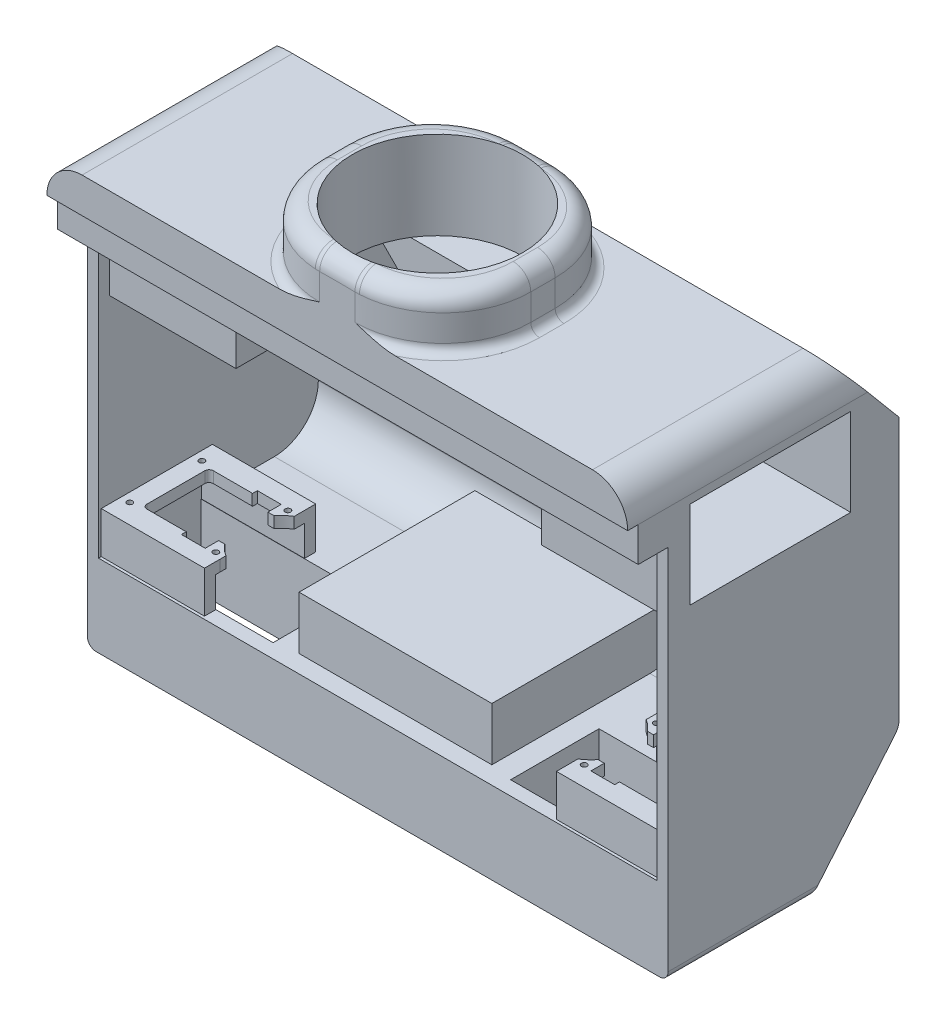
SolidWorks part; units mm, degrees
material "PLA"
ref_plane "Front Plane" through (0, 0, 0) normal (0, 0, 1) x (1, 0, 0)
ref_plane "Top Plane" through (0, 0, 0) normal (0, 1, 0) x (1, 0, 0)
ref_plane "Right Plane" through (0, 0, 0) normal (1, 0, 0) x (0, 0, -1)
sketch "Sketch1" plane through (0, 0, 0) normal (0, 1, 0) x (1, 0, 0)
  line L0 (0, -25.4) -> (0, 28.6) construction
  line L1 (-82.55, -25.4) -> (82.55, -25.4)
  line L2 (-82.55, -25.4) -> (-82.55, 28.6)
  line L3 (-82.55, 28.6) -> (82.55, 28.6)
  line L4 (82.55, -25.4) -> (82.55, 28.6)
  line L5 (-82.55, 1.6) -> (82.55, 1.6) construction
  point P4 (0, -25.4)
  point P5 (-82.55, 1.6)
  point P8 (0, 0)
  point P12 (0, 0)
  dimension "D1" = 165.1
  dimension "D2" = 54
extrude "Boss-Extrude1" add sketch "Sketch1" along normal blind 6.35
sketch "Sketch6" plane through (-82.55, 0, 0) normal (-1, 0, 0) x (0, 0, 1)
  line L1 (-37.0827, 90) -> (-37.0827, 6.35)
  line L4 (-40.2577, 90) -> (-37.0827, 90)
  line L7 (-28.6, 6.35) -> (-28.6, 0)
  line L8 (-28.6, 6.35) -> (-37.0827, 6.35)
  line L9 (-28.6, 0) -> (-40.2577, 0)
  line L10 (-40.2577, 0) -> (-40.2577, 90)
  dimension "D4" = 3.175
extrude "Boss-Extrude2" add sketch "Sketch6" against normal up to surface (165.1 mm away) up to face at (82.55, 3.175, -1.6)
sketch "Sketch7" plane through (0, 0, 25.4) normal (0, 0, 1) x (1, 0, 0)
  line L0 (-82.55, 0) -> (82.55, 0) construction
  line L1 (-82.55, 90) -> (-79.375, 90)
  line L2 (-82.55, 90) -> (-82.55, 0)
  line L3 (-82.55, 0) -> (-79.375, 0)
  line L4 (-79.375, 90) -> (-79.375, 0)
  line L6 (82.55, 0) -> (79.375, 0)
  line L7 (82.55, 0) -> (82.55, 90)
  line L8 (82.55, 90) -> (79.375, 90)
  line L9 (79.375, 0) -> (79.375, 90)
  dimension "D1" = 3.175
  dimension "D2" = 3.175
extrude "Boss-Extrude3" add sketch "Sketch7" against normal up to surface (62.4827 mm away) up to face at (0, 48.175, -37.0827)
sketch "Sketch9" plane through (0, 0, -40.2577) normal (0, 0, -1) x (-1, 0, 0)
  line L0 (-82.55, 0) -> (-82.55, 90) construction
  line L5 (82.55, 90) -> (82.55, 0) construction
  line L6 (-82.55, 0) -> (82.55, 0) construction
  line L7 (-82.55, 90) -> (82.55, 90) construction
  line L8 (-65.55, 83) -> (65.55, 83)
  line L9 (-67.55, 81) -> (-67.55, 32)
  line L10 (-65.55, 30) -> (65.55, 30)
  line L16 (67.55, 81) -> (67.55, 32)
  arc A0 (-67.55, 32) -> (-65.55, 30) centre (-65.55, 32) ccw
  arc A1 (65.55, 30) -> (67.55, 32) centre (65.55, 32) ccw
  arc A2 (65.55, 83) -> (67.55, 81) centre (65.55, 81) cw
  arc A3 (-65.55, 83) -> (-67.55, 81) centre (-65.55, 81) ccw
  dimension "D5" = 2
  dimension "D1" = 7
  dimension "D2" = 15
  dimension "D3" = 15
  dimension "D4" = 30
extrude "Boss-Extrude4" add sketch "Sketch9" along normal blind 1
sketch "Sketch10" plane through (-82.55, 0, 0) normal (-1, 0, 0) x (0, 0, 1)
  line L0 (25.4, 0) -> (25.4, 42.35) construction
  line L1 (25.4, 90) -> (25.4, 0) construction
  line L2 (25.4, 42.35) -> (-34.6, 42.35)
  line L3 (-34.6, 42.35) -> (-34.6, 90)
  line L5 (-34.6, 90) -> (25.4, 90)
  line L6 (25.4, 90) -> (25.4, 42.35)
  dimension "D1" = 42.35
  dimension "D2" = 60
extrude "Cut-Extrude2" cut sketch "Sketch10" against normal through all both and the other way through all
sketch "Sketch12" plane through (0, 90, 0) normal (0, 1, 0) x (1, 0, 0)
  line L3 (-82.55, -25.4) -> (-82.55, -30.4)
  line L4 (-82.55, 40.2577) -> (82.55, 40.2577)
  line L5 (82.55, 40.2577) -> (82.55, -25.4)
  line L7 (-82.55, -25.4) -> (-82.55, 40.2577)
  line L8 (-82.55, -30.4) -> (82.55, -30.4)
  line L9 (82.55, -30.4) -> (82.55, -25.4)
  dimension "D1" = 5
extrude "Boss-Extrude6" add sketch "Sketch12" along normal blind 3.175
sketch "Sketch15" plane through (0, 0, 0) normal (0, -1, 0) x (1, 0, 0)
  line L0 (82.55, 33.9) -> (82.55, -40.2577) construction
  line L1 (82.55, -3.1788) -> (-82.55, -3.1788) construction
  line L2 (-82.55, -40.2577) -> (-82.55, 25.4) construction
  line L3 (-82.55, 25.4) -> (82.55, 25.4) construction
  line L4 (-82.55, -3.1788) -> (-82.55, 8.8212) construction
  line L5 (-82.55, 8.8212) -> (82.55, 8.8212) construction
  line L6 (0, -3.1788) -> (0, 32.5085) construction
  line B0 (-66.875, 21.3812) -> (-66.875, 8.8212) construction
  line B1 (-33.755, 21.3812) -> (-79.375, 21.3812) construction
  line B2 (-33.755, -3.7388) -> (-79.375, -3.7388) construction
  line B3 (-33.755, 21.3812) -> (-33.755, -3.7388) construction
  line B4 (-79.375, -3.7388) -> (-79.375, 21.3812) construction
  line B5 (-46.255, 21.3812) -> (-46.255, 8.8212) construction
  line B6 (-79.375, -3.7388) -> (-33.755, -3.7388)
  line B7 (-79.375, -3.7388) -> (-79.375, 21.3812)
  line B8 (-79.375, 21.3812) -> (-33.755, 21.3812)
  line B9 (-33.755, -3.7388) -> (-33.755, 21.3812)
  circle B10 centre (-46.255, 8.8212) radius 3 construction
  line B11 (79.375, 21.3812) -> (33.755, 21.3812) construction
  line B12 (66.875, 21.3812) -> (66.875, 8.8212) construction
  line B13 (79.375, -3.7388) -> (33.755, -3.7388) construction
  line B14 (79.375, 21.3812) -> (79.375, -3.7388) construction
  line B15 (46.255, 21.3812) -> (46.255, 8.8212) construction
  line B16 (33.755, -3.7388) -> (33.755, 21.3812) construction
  line B17 (33.755, -3.7388) -> (79.375, -3.7388)
  line B18 (33.755, -3.7388) -> (33.755, 21.3812)
  line B19 (33.755, 21.3812) -> (79.375, 21.3812)
  line B20 (79.375, -3.7388) -> (79.375, 21.3812)
  circle B21 centre (46.255, 8.8212) radius 3 construction
  dimension "D1" = 3.175
  dimension "D2" = 3.175
  dimension "D3" = 12
sketch_block_instance "Block1-1"
sketch_block "Block1" parameters "D4"=6, "D1"=25.12, "D2"=45.62, "D3"=12.5, "D5"=12.5
sketch_block_instance "Block2-1"
sketch_block "Block2" parameters "D4"=6, "D1"=45.62, "D2"=12.5, "D3"=25.12, "D5"=12.5
extrude "Cut-Extrude3" cut sketch "Sketch15" against normal blind 10
sketch "Sketch16" plane through (0, 0, 0) normal (0, -1, 0) x (1, 0, 0)
  line L0 (33.755, -3.7388) -> (79.375, -3.7388) construction
  line L1 (-79.375, -3.7388) -> (-33.755, -3.7388)
  line L2 (-79.375, -3.7388) -> (-79.375, 21.3812)
  line L3 (-79.375, 21.3812) -> (-33.755, 21.3812)
  line L4 (82.55, -40.2577) -> (82.55, 25.4)
  line L5 (82.55, 25.4) -> (-82.55, 25.4)
  line L6 (-82.55, 25.4) -> (-82.55, -40.2577)
  line L7 (-82.55, -40.2577) -> (82.55, -40.2577)
  line L8 (82.55, -40.2577) -> (82.55, 25.4)
  line L9 (82.55, 25.4) -> (-82.55, 25.4)
  line L10 (-82.55, 25.4) -> (-82.55, -40.2577)
  line L11 (-82.55, -40.2577) -> (82.55, -40.2577)
  line L12 (-33.755, -3.7388) -> (-33.755, 21.3812)
  line L14 (33.755, 21.3812) -> (33.755, -3.7388)
  line L17 (79.375, -3.7388) -> (79.375, 21.3812) construction
  line L18 (79.375, 21.3812) -> (33.755, 21.3812) construction
  line L19 (33.755, -3.7388) -> (79.375, -3.7388)
  line L20 (79.375, -3.7388) -> (79.375, 21.3812)
  line L21 (79.375, 21.3812) -> (33.755, 21.3812)
  dimension "D1" = 0
extrude "Boss-Extrude7" add sketch "Sketch16" along normal blind 17
chamfer "Chamfer2" distance 4 angle 40 1 edges at (0, 93.175, -40.2577)
chamfer "Chamfer3" distance 30 angle 40 1 edges at (0, -17, -40.2577)
fillet "Fillet1" radius 12.5 1 edges at (0, 6.35, -37.0827)
fillet "Fillet2" radius 5 1 edges at (0, 13, -40.2577)
chamfer "Chamfer5" distance 3.175 angle 45 2 edges at (-80.9625, 90, -34.6) (80.9625, 90, -34.6)
chamfer "Chamfer6" distance 3.175 angle 45 2 edges at (80.9625, 42.35, -34.6) (-80.9625, 42.35, -34.6)
sketch "Sketch18" plane through (0, 93.175, 0) normal (0, 1, 0) x (1, 0, 0)
  line L0 (-82.8, 26.2862) -> (-82.8, 26.4862) construction
  line L1 (-83.35, 26.2862) -> (-82.25, 26.2862) construction
  line L2 (-82.55, 36.9013) -> (-82.55, -30.4) construction
  line L3 (-82.55, 36.9013) -> (-82.55, -30.4) construction
  line L4 (-82.8, 26.4862) -> (-46.5819, 26.4862) construction
  line L5 (-46.5819, 26.4862) -> (-46.5819, -19.9043) construction
  line L6 (-80.85, -18.9297) -> (-80.85, -19.1297) construction
  line L7 (-82.55, -19.1297) -> (-46.5819, -19.1297)
  line L8 (-46.5819, -19.1297) -> (-46.5819, 26.4862)
  line L9 (-80.85, -18.9297) -> (-74.95, -18.9297)
  line L10 (-74.95, -18.9297) -> (-74.95, -18.2883)
  line L11 (-74.95, -18.2883) -> (-80.85, -18.2883)
  line L12 (-80.85, -18.9297) -> (-74.95, -18.9297)
  line L13 (-46.5819, 26.4862) -> (-82.55, 26.4862)
  line L15 (-82.55, -22.3047) -> (-43.4069, -22.3047)
  line L16 (-43.4069, -22.3047) -> (-43.4069, 29.6612)
  line L17 (-43.4069, 29.6612) -> (-82.55, 29.6612)
  line L18 (-82.55, 29.6612) -> (-82.55, 26.4862)
  line L19 (-82.55, -22.3047) -> (-82.55, -19.1297)
  spline S1 degree 3 poles (-1054.8455, 208.2772) (893.5385, -208.2061) (-1055.3981, 170.5876) (893.6165, -243.4552) knots -0.027165 -0.027165 -0.027165 -0.027165 0.027597 0.027597 0.027597 0.027597 only from (-80.85, -18.2883) to (-80.85, -18.9297)
  dimension "D1" = 0.2
  dimension "D3" = 0.2
  dimension "D2" = 0
  dimension "D4" = 3.175
extrude "Boss-Extrude9" add sketch "Sketch18" against normal blind 20.535
mirror "Mirror1" about plane through (0, 0, 0) normal (1, 0, 0) of "Boss-Extrude9"
sketch "Sketch20" plane through (0, 0, 30.4) normal (0, 0, 1) x (1, 0, 0)
  line L3 (-52.55, 99.8258) -> (52.55, 99.8258)
  line L4 (-82.55, 93.175) -> (82.55, 93.175)
  line L5 (-52.55, 99.8258) -> (-82.55, 99.8258)
  line L6 (-82.55, 99.8258) -> (-82.55, 93.175)
  line L7 (52.55, 99.8258) -> (82.55, 99.8258)
  line L8 (82.55, 99.8258) -> (82.55, 93.175)
  dimension "D3" = 30
  dimension "D4" = 30
extrude "Boss-Extrude10" add sketch "Sketch20" against normal up to surface (61.7206 mm away)
sketch "Sketch23" plane through (0, 99.8258, 0) normal (0, 1, 0) x (1, 0, 0)
  line L12 (8.3844, -20.5613) -> (9.8774, -19.0684)
  line L13 (10.6096, -17.3007) -> (10.6096, 0.4337)
  line L14 (9.8774, 2.2013) -> (8.3844, 3.6943)
  line L15 (6.6168, 4.4265) -> (-33.1106, 4.4265)
  line L16 (-35.6104, 1.9267) -> (-35.6104, -18.7937)
  line L17 (-33.1106, -21.2935) -> (6.6168, -21.2935)
  line L18 (8.3844, -20.5613) -> (9.8774, -19.0684)
  line L19 (10.6096, -17.3007) -> (10.6096, 0.4337)
  line L20 (9.8774, 2.2013) -> (8.3844, 3.6943)
  line L21 (6.6168, 4.4265) -> (-33.1106, 4.4265)
  line L22 (-35.6104, 1.9267) -> (-35.6104, -18.7937)
  line L23 (-33.1106, -21.2935) -> (6.6168, -21.2935)
  arc A22 (6.6168, -21.2935) -> (7.5734, -21.1032) centre (6.6168, -18.7937) ccw
  arc A23 (7.5734, -21.1032) -> (8.3844, -20.5613) centre (6.6168, -18.7937) ccw
  arc A24 (9.8774, -19.0684) -> (10.4193, -18.2574) centre (8.1098, -17.3007) ccw
  arc A25 (10.4193, -18.2574) -> (10.6096, -17.3007) centre (8.1098, -17.3007) ccw
  arc A26 (10.6096, 0.4337) -> (10.4193, 1.3903) centre (8.1098, 0.4337) ccw
  arc A27 (10.4193, 1.3903) -> (9.8774, 2.2013) centre (8.1098, 0.4337) ccw
  arc A28 (8.3844, 3.6943) -> (7.5734, 4.2362) centre (6.6168, 1.9267) ccw
  arc A29 (7.5734, 4.2362) -> (6.6168, 4.4265) centre (6.6168, 1.9267) ccw
  arc A30 (-33.1106, 4.4265) -> (-35.6104, 1.9267) centre (-33.1107, 1.9268) ccw
  arc A31 (-35.6104, -18.7937) -> (-34.8783, -20.5614) centre (-33.1106, -18.7938) ccw
  arc A32 (-34.8783, -20.5614) -> (-33.1106, -21.2935) centre (-33.1107, -18.7937) ccw
  arc A33 (6.6168, -21.2935) -> (7.5734, -21.1032) centre (6.6168, -18.7937) ccw
  arc A34 (7.5734, -21.1032) -> (8.3844, -20.5613) centre (6.6168, -18.7937) ccw
  arc A35 (9.8774, -19.0684) -> (10.4193, -18.2574) centre (8.1098, -17.3007) ccw
  arc A36 (10.4193, -18.2574) -> (10.6096, -17.3007) centre (8.1098, -17.3007) ccw
  arc A37 (10.6096, 0.4337) -> (10.4193, 1.3903) centre (8.1098, 0.4337) ccw
  arc A38 (10.4193, 1.3903) -> (9.8774, 2.2013) centre (8.1098, 0.4337) ccw
  arc A39 (8.3844, 3.6943) -> (7.5734, 4.2362) centre (6.6168, 1.9267) ccw
  arc A40 (7.5734, 4.2362) -> (6.6168, 4.4265) centre (6.6168, 1.9267) ccw
  arc A41 (-33.1106, 4.4265) -> (-35.6104, 1.9267) centre (-33.1107, 1.9268) ccw
  arc A42 (-35.6104, -18.7937) -> (-34.8783, -20.5614) centre (-33.1106, -18.7938) ccw
  arc A43 (-34.8783, -20.5614) -> (-33.1106, -21.2935) centre (-33.1107, -18.7937) ccw
  dimension "D1" = 0.5
extrude "Cut-Extrude4" cut sketch "Sketch23" against normal blind 20
ref_plane "Plane1" through (-82.55, 99.8258, 30.4) normal (-1, 0, 0) x (0, 0, 1)
sketch "Sketch25" plane through (0, 99.8258, 0) normal (0, 1, 0) x (1, 0, 0)
  line L10 (-82.55, 24.6) -> (-82.55, -85.4) construction
  line L11 (82.55, -30.4) -> (-82.55, -30.4) construction
  line L12 (-82.55, -30.4) -> (-82.55, 31.3206)
  line L13 (-82.55, 31.3206) -> (82.55, 31.3206)
  line L14 (82.55, 31.3206) -> (82.55, -30.4)
  line L16 (-82.55, -30.4) -> (-82.55, -36.9)
  line L17 (82.55, -30.4) -> (82.55, -36.9)
  line L18 (82.55, -36.9) -> (-82.55, -36.9)
  circle A0 centre (-0.0004, -8.4335) radius 4.328
  circle A4 centre (-0.0004, -8.4335) radius 24.2
  point P3 (24.1996, -8.4335)
  point P20 (22.9509, -1.4166)
  dimension "D1" = 6.5
extrude "Boss-Extrude11" add sketch "Sketch25" along normal blind 10
chamfer "Chamfer9" distance 10 angle 40 1 edges at (0, 109.8258, -31.3206)
sketch "Sketch26" plane through (0, 109.8258, 0) normal (0, 1, 0) x (1, 0, 0)
  line L1 (-30.0004, -36.9) -> (-30.0004, 20.0365)
  line L6 (-30.0004, 20.0365) -> (29.9996, 20.0365)
  line L11 (29.9996, 20.0365) -> (29.9996, -36.9)
  line L12 (-30.0004, -36.9) -> (29.9996, -36.9)
  line L15 (82.55, -36.9) -> (-82.55, -36.9) construction
  circle A4 centre (-0.0004, -8.4335) radius 24.2
  dimension "D1" = 28.47
extrude "Boss-Extrude12" add sketch "Sketch26" along normal blind 15
sketch "Sketch27" plane through (0, 0, 30.4) normal (0, 0, 1) x (1, 0, 0)
  line L8 (82.55, 90) -> (82.55, 99.8258)
  line L10 (82.55, 99.8258) -> (10.154, 99.8258)
  line L11 (10.154, 99.8258) -> (-10.1549, 99.8258)
  line L12 (-10.1549, 99.8258) -> (-82.55, 99.8258)
  line L14 (-82.55, 99.8258) -> (-82.55, 90)
  line L15 (-82.55, 90) -> (82.55, 90)
  line L16 (82.55, 90) -> (82.55, 99.8258)
  line L18 (82.55, 99.8258) -> (10.154, 99.8258)
  line L19 (10.154, 99.8258) -> (-10.1549, 99.8258)
  line L20 (-10.1549, 99.8258) -> (-82.55, 99.8258)
  line L22 (-82.55, 99.8258) -> (-82.55, 90)
  line L23 (-82.55, 90) -> (82.55, 90)
  dimension "D1" = 0
extrude "Boss-Extrude13" add sketch "Sketch27" along normal blind 3.5
fillet "Fillet6" radius 25 4 edges at (-30.0004, 117.3258, -20.0365) (29.9996, 117.3258, -20.0365) (-30.0004, 117.3258, 36.9) (29.9996, 117.3258, 36.9)
fillet "Fillet7" radius 5 6 edges at (22.6772, 124.8258, -12.7142) (29.9996, 124.8258, 8.4318) (22.6772, 124.8258, 29.5777) (-22.6781, 124.8258, 29.5777) (-30.0004, 124.8258, 8.4318) (-22.6781, 124.8258, -12.7142)
sketch "Sketch28" plane through (0, 90, 0) normal (0, -1, 0) x (1, 0, 0)
  line L4 (46.5819, -26.4862) -> (82.55, -26.4862)
  line L5 (82.55, -26.4862) -> (82.55, 19.1297)
  line L6 (82.55, 19.1297) -> (46.5819, 19.1297)
  line L7 (46.5819, 19.1297) -> (46.5819, -26.4862)
  line L8 (46.5819, -26.4862) -> (82.55, -26.4862)
  line L9 (82.55, -26.4862) -> (82.55, 19.1297)
  line L10 (82.55, 19.1297) -> (46.5819, 19.1297)
  line L11 (46.5819, 19.1297) -> (46.5819, -26.4862)
  dimension "D1" = 0
extrude "Cut-Extrude5" cut sketch "Sketch28" against normal blind 7.5
sketch "Sketch29" plane through (0, 90, 0) normal (0, -1, 0) x (1, 0, 0)
  line L4 (-46.5819, -26.4862) -> (-46.5819, 19.1297)
  line L5 (-46.5819, 19.1297) -> (-82.55, 19.1297)
  line L6 (-82.55, 19.1297) -> (-82.55, -26.4862)
  line L7 (-82.55, -26.4862) -> (-46.5819, -26.4862)
  line L8 (-46.5819, -26.4862) -> (-46.5819, 19.1297)
  line L9 (-46.5819, 19.1297) -> (-82.55, 19.1297)
  line L10 (-82.55, 19.1297) -> (-82.55, -26.4862)
  line L11 (-82.55, -26.4862) -> (-46.5819, -26.4862)
  dimension "D1" = 0
extrude "Cut-Extrude6" cut sketch "Sketch29" against normal blind 7.5
fillet "Fillet8" radius 10 2 edges at (82.55, 109.8258, 6.9852) (-82.55, 109.8258, 6.9852)
fillet "Fillet9" radius 2.5 2 edges at (82.55, -17, 5.1576) (-82.55, -17, 5.1576)
sketch "Sketch30" plane through (-43.4069, 0, 0) normal (1, 0, 0) x (0, 0, -1)
  line L0 (-3.3585, 96.4) -> (-3.3585, 95.1073)
  line L1 (-3.3585, 95.1073) -> (2.3742, 91.54)
  line L3 (2.3742, 78.54) -> (-3.3585, 74.9727)
  line L4 (-3.3585, 74.9727) -> (-3.3585, 73.68)
  line L5 (-3.3585, 73.68) -> (-2.3585, 72.68)
  line L6 (-2.3585, 72.68) -> (24.2902, 72.68)
  line L7 (24.2902, 72.68) -> (26.29, 74.6798)
  line L8 (26.29, 74.6798) -> (26.2862, 95.2064)
  line L9 (26.2862, 95.2064) -> (24.1801, 97.4)
  line L10 (24.1801, 97.4) -> (-2.3585, 97.4)
  line L11 (-2.3585, 97.4) -> (-3.3585, 96.4)
  line L12 (2.3742, 91.54) -> (2.3742, 95.64)
  line L13 (2.3742, 95.64) -> (7.9598, 95.64)
  line L14 (7.9598, 95.64) -> (8.505, 94.5648)
  line L15 (8.505, 94.5648) -> (21.8381, 94.5648)
  line L16 (2.3742, 78.54) -> (2.3742, 74.44)
  line L17 (2.3742, 74.44) -> (7.9598, 74.44)
  line L18 (7.9598, 74.44) -> (8.505, 75.4895)
  line L19 (8.505, 75.4895) -> (21.8381, 75.4895)
  line L20 (21.8381, 75.4895) -> (21.8381, 94.5648)
  circle A0 centre (-0.52, 95.29) radius 0.8
  circle A1 centre (23.93, 95.29) radius 0.8
  circle A2 centre (23.93, 74.79) radius 0.8
  circle A3 centre (-0.52, 74.79) radius 0.8
sketch "Sketch31" plane through (-43.4069, 0, 0) normal (1, 0, 0) x (0, 0, -1)
  line L0 (2.3742, 95.64) -> (2.3742, 74.44)
  line L1 (2.3742, 74.44) -> (7.9598, 74.44)
  line L2 (7.9598, 74.44) -> (7.9598, 95.64)
  line L3 (7.9598, 95.64) -> (2.3742, 95.64)
extrude "Cut-Extrude7" cut sketch "Sketch31" against normal blind 10
extrude "Boss-Extrude14" add sketch "Sketch30" against normal blind 7.08
sketch "Sketch33" plane through (0, 90, 0) normal (0, -1, 0) x (1, 0, 0)
  line L1 (-43.4069, -29.6612) -> (-31.4069, -29.6612)
  line L2 (-43.4069, -29.6612) -> (-43.4069, 22.3047)
  line L3 (-43.4069, 22.3047) -> (-31.4069, 22.3047)
  line L4 (-31.4069, -29.6612) -> (-31.4069, 22.3047)
  line L5 (43.4069, -29.6612) -> (31.4069, -29.6612)
  line L6 (43.4069, -29.6612) -> (43.4069, 22.3047)
  line L7 (43.4069, 22.3047) -> (31.4069, 22.3047)
  line L8 (31.4069, -29.6612) -> (31.4069, 22.3047)
  dimension "D1" = 12
  dimension "D2" = 12
extrude "Cut-Extrude9" cut sketch "Sketch33" against normal blind 7.5
chamfer "Chamfer12" distance 7.5 angle 45 3 edges at (-31.4069, 90, 21.7991) (-31.4069, 90, -17.0439) (31.4069, 90, -3.6783)
mirror "Mirror2" about plane through (0, 0, 0) normal (1, 0, 0) of "Boss-Extrude14", "Cut-Extrude7"
sketch "Sketch36" plane through (-82.55, 0, 0) normal (-1, 0, 0) x (0, 0, 1)
  line L0 (-29.6612, 72.64) -> (-29.6612, 90)
  line L1 (-29.6612, 90) -> (-31.425, 90)
  line L2 (-31.425, 90) -> (-34.6, 86.825)
  line L3 (-34.6, 86.825) -> (-34.6, 45.525)
  line L4 (-34.6, 45.525) -> (-31.425, 42.35)
  line L5 (-31.425, 42.35) -> (25.4, 42.35)
  line L6 (25.4, 42.35) -> (25.4, 90)
  line L7 (22.3047, 90) -> (33.9, 90) construction
  line L8 (25.4, 90) -> (22.3047, 90)
  line L9 (22.3047, 90) -> (22.3047, 72.64)
  line L10 (22.3047, 72.64) -> (-29.6612, 72.64)
extrude "Boss-Extrude15" add sketch "Sketch36" against normal blind 3.175
sketch "Sketch37" plane through (0, 72.64, 0) normal (0, -1, 0) x (1, 0, 0)
  line L0 (-79.375, 22.3047) -> (-79.375, -29.6612)
  line L8 (-43.4069, 22.3047) -> (-79.375, 22.3047)
  line L9 (-79.375, 22.3047) -> (-79.375, 19.1297)
  line L10 (-79.375, 19.1297) -> (-46.5819, 19.1297)
  line L11 (-46.5819, 19.1297) -> (-46.5819, -26.4862)
  line L12 (-46.5819, -26.4862) -> (-79.375, -26.4862)
  line L13 (-79.375, -26.4862) -> (-79.375, -29.6612)
  line L14 (-79.375, -29.6612) -> (-43.4069, -29.6612)
  line L15 (-43.4069, -29.6612) -> (-43.4069, 22.3047)
  line L16 (-43.4069, 22.3047) -> (-79.375, 22.3047)
  line L17 (-79.375, 22.3047) -> (-79.375, 19.1297)
  line L21 (-79.375, -26.4862) -> (-79.375, -29.6612)
  line L22 (-79.375, -29.6612) -> (-43.4069, -29.6612)
  line L23 (-43.4069, -29.6612) -> (-43.4069, 22.3047)
  line M9 (-43.4069, 22.3047) -> (-79.375, 22.3047)
  line M10 (-79.375, 22.3047) -> (-79.375, 19.1297)
  line M11 (-79.375, 19.1297) -> (-46.5819, 19.1297)
  line M12 (-46.5819, 19.1297) -> (-46.5819, -26.4862)
  line M13 (-46.5819, -26.4862) -> (-79.375, -26.4862)
  line M14 (-79.375, -26.4862) -> (-79.375, -29.6612)
  line M15 (-79.375, -29.6612) -> (-43.4069, -29.6612)
  line M16 (-43.4069, -29.6612) -> (-43.4069, 22.3047)
  dimension "D1" = 0
extrude "Boss-Extrude16" add sketch "Sketch37" along normal blind 3.175 contours L0 M11 M13 M12 | M16 M9 M10 M11 M12 M13 M14 M15
sketch "Sketch42" plane through (-50.4869, 0, 0) normal (-1, 0, 0) x (0, 0, 1)
  circle A0 centre (-23.93, 74.79) radius 0.8 construction
  circle A1 centre (0.52, 74.79) radius 0.8 construction
  circle A2 centre (0.52, 95.29) radius 0.8 construction
  circle A3 centre (-23.93, 95.29) radius 0.8 construction
  circle A4 centre (-23.93, 74.79) radius 0.8
  circle A5 centre (0.52, 74.79) radius 0.8
  circle A6 centre (0.52, 95.29) radius 0.8
  circle A7 centre (-23.93, 95.29) radius 0.8
extrude "Cut-Extrude10" cut sketch "Sketch42" against normal blind 8
mirror "Mirror3" about plane through (0, 0, 0) normal (1, 0, 0) of "Cut-Extrude10", "Boss-Extrude15", "Boss-Extrude16"
ref_plane "Plane2" through (0, 15, 0) normal (0, 1, 0) x (1, 0, 0)
sketch "Sketch39" plane through (0, 15, 0) normal (0, 1, 0) x (1, 0, 0)
  line L0 (-50.0265, 2.5388) -> (-50.0265, 6.9853)
  line L1 (-50.0265, 6.9853) -> (-82.55, 6.9853)
  line L2 (-82.55, 24.6) -> (-82.55, -85.4) construction
  line L3 (-82.55, 6.9853) -> (-82.55, 3.0389)
  line L4 (-50.0265, -20.1811) -> (-50.0265, -24.6276)
  line L5 (-50.0265, -24.6276) -> (-82.55, -24.6276)
  line L6 (-82.55, -24.6276) -> (-82.55, -20.6812)
  line L73 (-82.55, 17.1825) -> (-82.55, -25.4) construction
  line L75 (-82.55, 3.0389) -> (-82.55, -20.6812)
  line L90 (-54.815, -15.8212) -> (-54.815, -19.6212)
  line L91 (-54.815, -19.6212) -> (-61.59, -19.6212)
  line L92 (-61.59, -19.6212) -> (-61.59, -18.1242)
  line L93 (-61.59, -18.1242) -> (-61.8129, -18.2634)
  line L94 (-61.8129, -18.2634) -> (-72.7681, -18.2634)
  line L95 (-73.9681, -17.0634) -> (-73.9681, -0.5789)
  line L96 (-72.7681, 0.6211) -> (-61.8129, 0.6211)
  line L97 (-61.8129, 0.6211) -> (-61.59, 0.4819)
  line L98 (-61.59, 0.4819) -> (-61.59, 1.9788)
  line L99 (-61.59, 1.9788) -> (-54.815, 1.9788)
  line L100 (-54.815, 1.9788) -> (-54.815, -1.8212)
  line L101 (-54.815, -1.8212) -> (-53.0514, -1.8212)
  line L102 (-50.0265, 0.8853) -> (-50.0265, 2.5388)
  line L103 (-50.5265, 3.0388) -> (-77.1753, 3.0389)
  line L104 (-78.675, 1.539) -> (-78.675, -19.1814)
  line L105 (-77.1752, -20.6812) -> (-50.5265, -20.6812)
  line L106 (-50.0265, -20.1811) -> (-50.0265, -18.5276)
  line L107 (-53.0514, -15.8212) -> (-54.815, -15.8212)
  line L108 (-54.815, -15.8212) -> (-54.815, -19.6212)
  line L109 (-54.815, -19.6212) -> (-61.59, -19.6212)
  line L110 (-61.59, -19.6212) -> (-61.59, -18.1242)
  line L111 (-61.59, -18.1242) -> (-61.8129, -18.2634)
  line L112 (-61.8129, -18.2634) -> (-72.7681, -18.2634)
  line L113 (-73.9681, -17.0634) -> (-73.9681, -0.5789)
  line L114 (-72.7681, 0.6211) -> (-61.8129, 0.6211)
  line L115 (-61.8129, 0.6211) -> (-61.59, 0.4819)
  line L116 (-61.59, 0.4819) -> (-61.59, 1.9788)
  line L117 (-61.59, 1.9788) -> (-54.815, 1.9788)
  line L118 (-54.815, 1.9788) -> (-54.815, -1.8212)
  line L119 (-54.815, -1.8212) -> (-53.0514, -1.8212)
  line L120 (-50.0265, 0.8853) -> (-50.0265, 2.5388)
  line L124 (-50.0265, -20.1811) -> (-50.0265, -18.5276)
  line L125 (-53.0514, -15.8212) -> (-54.815, -15.8212)
  arc A0 (-53.165, -19.0712) -> (-51.565, -19.0712) centre (-52.365, -19.0712) ccw
  arc A1 (-51.565, -19.0712) -> (-53.165, -19.0712) centre (-52.365, -19.0712) ccw
  arc A2 (-53.165, -19.0712) -> (-51.565, -19.0712) centre (-52.365, -19.0712) ccw
  arc A3 (-51.565, -19.0712) -> (-53.165, -19.0712) centre (-52.365, -19.0712) ccw
  arc A4 (-51.565, 1.4288) -> (-53.165, 1.4288) centre (-52.365, 1.4288) ccw
  arc A5 (-53.165, 1.4288) -> (-51.565, 1.4288) centre (-52.365, 1.4288) ccw
  arc A6 (-51.565, 1.4288) -> (-53.165, 1.4288) centre (-52.365, 1.4288) ccw
  arc A7 (-53.165, 1.4288) -> (-51.565, 1.4288) centre (-52.365, 1.4288) ccw
  arc A8 (-76.015, -19.0712) -> (-77.615, -19.0712) centre (-76.815, -19.0712) ccw
  arc A9 (-77.615, -19.0712) -> (-76.015, -19.0712) centre (-76.815, -19.0712) ccw
  arc A10 (-76.015, -19.0712) -> (-77.615, -19.0712) centre (-76.815, -19.0712) ccw
  arc A11 (-77.615, -19.0712) -> (-76.015, -19.0712) centre (-76.815, -19.0712) ccw
  arc A12 (-76.015, 1.4288) -> (-77.615, 1.4288) centre (-76.815, 1.4288) ccw
  arc A13 (-77.615, 1.4288) -> (-76.015, 1.4288) centre (-76.815, 1.4288) ccw
  arc A14 (-76.015, 1.4288) -> (-77.615, 1.4288) centre (-76.815, 1.4288) ccw
  arc A15 (-77.615, 1.4288) -> (-76.015, 1.4288) centre (-76.815, 1.4288) ccw
  arc A30 (-73.9681, -17.0634) -> (-72.7681, -18.2634) centre (-72.7681, -17.0634) ccw
  arc A31 (-72.7681, 0.6211) -> (-73.9681, -0.5789) centre (-72.7681, -0.5789) ccw
  arc A32 (-50.0265, 0.8853) -> (-53.0514, -1.8212) centre (-44.065, -8.8212) ccw
  arc A33 (-50.0265, 2.5388) -> (-50.5265, 3.0388) centre (-50.5265, 2.5388) ccw
  arc A34 (-50.5265, -20.6812) -> (-50.0265, -20.1811) centre (-50.5265, -20.1812) ccw
  arc A35 (-53.0514, -15.8212) -> (-50.0265, -18.5276) centre (-44.065, -8.8212) ccw
  arc A36 (-73.9681, -17.0634) -> (-72.7681, -18.2634) centre (-72.7681, -17.0634) ccw
  arc A37 (-72.7681, 0.6211) -> (-73.9681, -0.5789) centre (-72.7681, -0.5789) ccw
  arc A38 (-50.0265, 0.8853) -> (-53.0514, -1.8212) centre (-44.065, -8.8212) ccw
  arc A41 (-53.0514, -15.8212) -> (-50.0265, -18.5276) centre (-44.065, -8.8212) ccw
  spline S10 degree 3 poles (117.9821, -977.732) (-44.9346, -76.9424) (-68.3224, 4.8348) (-77.5634, 2.9908) (-77.6586, 2.962) (-77.8401, 2.8869) (-77.9262, 2.8407) (-78.0891, 2.7319) (-78.1664, 2.6687) (-78.3738, 2.4614) (-78.4855, 2.2942) (-81.5331, -5.0564) (-29.9638, -38.085) (457.0881, 845.8835) knots -11.807339 -11.807339 -11.807339 -11.807339 0.125 0.125 0.25 0.25 0.375 0.375 0.5 0.5 0.75 0.75 10.692244 10.692244 10.692244 10.692244 only from (-77.1753, 3.0389) to (-78.675, 1.539)
  spline S11 degree 3 poles (902.0998, 175.9554) (1.3026, 13.0565) (-80.4707, -10.3287) (-78.6269, -19.5695) (-78.5982, -19.6647) (-78.523, -19.8463) (-78.4769, -19.9323) (-78.3681, -20.0953) (-78.3049, -20.1725) (-78.0976, -20.3799) (-77.9304, -20.4917) (-70.58, -23.5394) (-37.5509, 28.0266) (-921.4585, 515.1761) knots -11.80709 -11.80709 -11.80709 -11.80709 0.125 0.125 0.25 0.25 0.375 0.375 0.5 0.5 0.75 0.75 10.692143 10.692143 10.692143 10.692143 only from (-78.675, -19.1814) to (-77.1752, -20.6812)
  dimension "D6" = 6.1
  dimension "D7" = 6.1
  dimension "D1" = 0.2
  dimension "D2" = 0
  dimension "D3" = 0
  dimension "D4" = 0
  dimension "D5" = 0
extrude "Boss-Extrude17" add sketch "Sketch39" along normal blind 3.175
sketch "Sketch41" plane through (0, 15, 0) normal (0, -1, 0) x (1, 0, 0)
  line L0 (-50.0265, 24.6276) -> (-50.0265, 21.4526)
  line L1 (-50.0265, 21.4526) -> (-79.375, 21.4526)
  line L2 (-50.0265, -6.9853) -> (-50.0265, -3.8103)
  line L3 (-50.0265, -3.8103) -> (-79.375, -3.8103)
  line L4 (-79.375, -3.8103) -> (-79.375, -6.9853)
  line L20 (-79.375, 24.6276) -> (-79.375, -6.9853)
  line L21 (-79.375, -6.9853) -> (-50.0265, -6.9853)
  line L22 (-50.0265, -6.9853) -> (-50.0265, -2.5388)
  line L23 (-50.0265, -2.5388) -> (-50.0265, -0.8853)
  line L24 (-53.0514, 1.8212) -> (-54.815, 1.8212)
  line L25 (-54.815, 1.8212) -> (-54.815, -1.9788)
  line L26 (-54.815, -1.9788) -> (-61.59, -1.9788)
  line L27 (-61.59, -1.9788) -> (-61.59, -0.4819)
  line L28 (-61.59, -0.4819) -> (-61.8129, -0.6211)
  line L29 (-61.8129, -0.6211) -> (-72.7681, -0.6211)
  line L30 (-73.9681, 0.5789) -> (-73.9681, 17.0634)
  line L31 (-72.7681, 18.2634) -> (-61.8129, 18.2634)
  line L32 (-61.8129, 18.2634) -> (-61.59, 18.1242)
  line L33 (-61.59, 18.1242) -> (-61.59, 19.6212)
  line L34 (-61.59, 19.6212) -> (-54.815, 19.6212)
  line L35 (-54.815, 19.6212) -> (-54.815, 15.8212)
  line L36 (-54.815, 15.8212) -> (-53.0514, 15.8212)
  line L37 (-50.0265, 18.5276) -> (-50.0265, 20.1811)
  line L38 (-50.0265, 20.1811) -> (-50.0265, 24.6276)
  line L39 (-50.0265, 24.6276) -> (-79.375, 24.6276)
  line L40 (-79.375, 24.6276) -> (-79.375, 21.4526)
  line L41 (-79.375, -6.9853) -> (-50.0265, -6.9853)
  line L59 (-50.0265, 24.6276) -> (-79.375, 24.6276)
  arc A4 (-53.0514, 1.8212) -> (-50.0265, -0.8853) centre (-44.065, 8.8212) ccw
  arc A5 (-73.9681, 0.5789) -> (-72.7681, -0.6211) centre (-72.7681, 0.5789) ccw
  arc A6 (-72.7681, 18.2634) -> (-73.9681, 17.0634) centre (-72.7681, 17.0634) ccw
  arc A7 (-50.0265, 18.5276) -> (-53.0514, 15.8212) centre (-44.065, 8.8212) ccw
  dimension "D2" = 3.175
  dimension "D3" = 3.175
  dimension "D1" = 0
extrude "Boss-Extrude19" add sketch "Sketch41" along normal up to surface (8.65 mm away) up to face at (0, 6.35, 6.017)
mirror "Mirror4" about plane through (0, 0, 0) normal (1, 0, 0) of "Boss-Extrude19", "Boss-Extrude17"
sketch "Sketch43" plane through (0, 6.35, 0) normal (0, 1, 0) x (1, 0, 0)
  line L0 (-79.375, -25.4) -> (79.375, -25.4) construction
  line L1 (-27.405, 29.63) -> (27.405, 29.63)
  line L2 (-27.405, 29.63) -> (-27.405, -20.37)
  line L3 (-27.405, -20.37) -> (27.405, -20.37)
  line L4 (27.405, 29.63) -> (27.405, -20.37)
  line L5 (-33.755, 3.7388) -> (-33.755, -21.3812) construction
  line L6 (33.755, -21.3812) -> (33.755, 3.7388) construction
  line M16 (79.375, 24.5827) -> (-79.375, 24.5827)
  dimension "D1" = 5.03
  dimension "D2" = 50
  dimension "D3" = 6.35
  dimension "D4" = 6.35
extrude "Boss-Extrude20" add sketch "Sketch43" along normal blind 15.1 contours L4 L2 L3 M16 | L4 L1 L2 M16
fillet "Fillet11" radius 2.5 7 edges at (-22.6781, 109.8258, 29.5777) (-30.0004, 109.8258, 8.4318) (22.6772, 109.8258, 29.5777) (29.9996, 109.8258, 8.4318) (22.6772, 109.8258, -12.7142) (-0.0004, 109.8258, -20.0365) (-22.6781, 109.8258, -12.7142)
